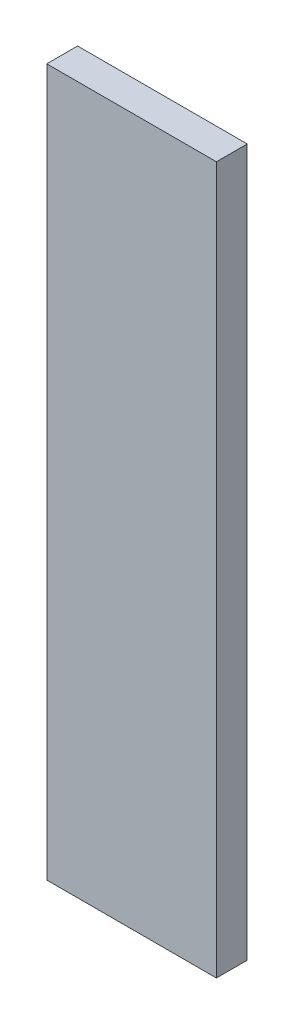
SolidWorks part; units mm, degrees
ref_plane "Front Plane" through (0, 0, 0) normal (0, 0, 1) x (1, 0, 0)
ref_plane "Top Plane" through (0, 0, 0) normal (0, 1, 0) x (1, 0, 0)
ref_plane "Right Plane" through (0, 0, 0) normal (1, 0, 0) x (0, 0, -1)
sketch "Sketch1" plane through (0, 0, 0) normal (0, 0, 1) x (1, 0, 0)
  line L1 (-23, 0) -> (43, 0)
  line L2 (-23, 0) -> (-23, 275)
  line L3 (-23, 275) -> (43, 275)
  line L4 (43, 0) -> (43, 275)
  line L5 (23, 255) -> (-23, 255)
  line L6 (23, 255) -> (23, 0)
  line L7 (23, 0) -> (-23, 0)
  line L8 (-23, 255) -> (-23, 0)
  dimension "D1" = 20
  dimension "D2" = 20
extrude "Boss-Extrude1" add sketch "Sketch1" against normal blind 6 contours L5 L6 L1 L4 L3 L2 region at (28.271, 155.771, 0)
sketch "Sketch2" plane through (0, 0, 0) normal (0, 0, 1) x (1, 0, 0)
  line L1 (43, 275) -> (-23, 275)
  line L2 (43, 275) -> (43, 0)
  line L3 (43, 0) -> (-23, 0)
  line L4 (-23, 275) -> (-23, 0)
extrude "Boss-Extrude2" add sketch "Sketch2" along normal blind 6
